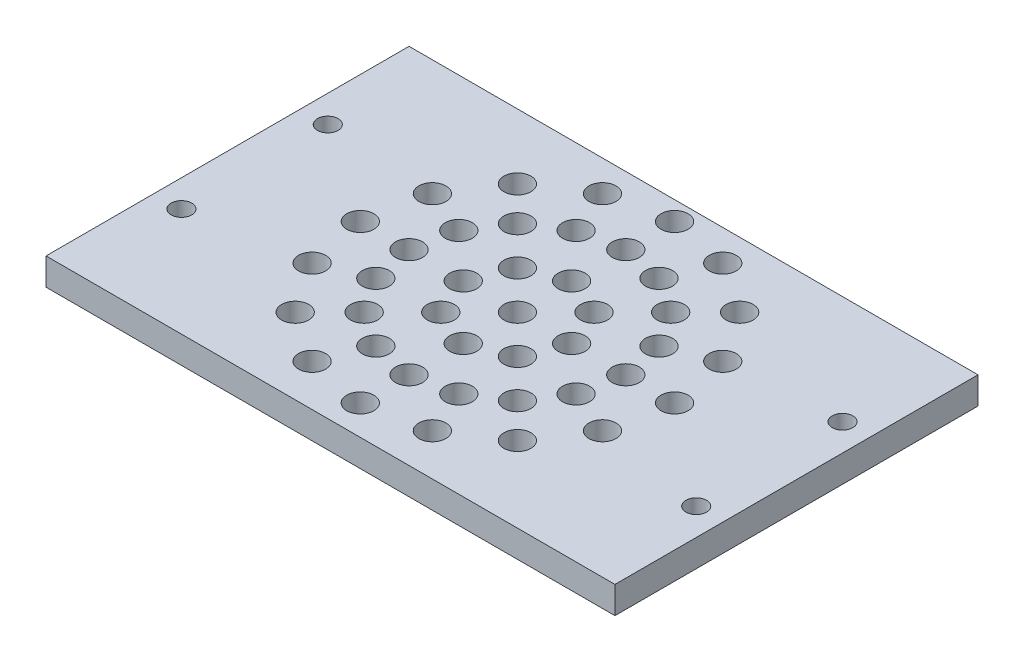
SolidWorks part; units mm, degrees
material "1060 Alloy"
ref_plane "Front Plane" through (0, 0, 0) normal (0, 0, 1) x (1, 0, 0)
ref_plane "Top Plane" through (0, 0, 0) normal (0, 1, 0) x (1, 0, 0)
ref_plane "Right Plane" through (0, 0, 0) normal (1, 0, 0) x (0, 0, -1)
sketch "Sketch1" plane through (0, 0, 0) normal (0, 1, 0) x (1, 0, 0)
  line L1 (-45.1884, 47.6545) -> (88.1616, 47.6545)
  line L2 (-45.1884, 47.6545) -> (-45.1884, -37.4355)
  line L3 (-45.1884, -37.4355) -> (88.1616, -37.4355)
  line L4 (88.1616, 47.6545) -> (88.1616, -37.4355)
  dimension "D1" = 133.35
  dimension "D2" = 85.09
extrude "Boss-Extrude1" add sketch "Sketch1" along normal blind 6.35
sketch "Sketch2" plane through (0, 6.35, 0) normal (0, 1, 0) x (1, 0, 0)
  line L0 (88.1616, -37.4355) -> (88.1616, 47.6545) construction
  line L1 (-45.1884, -37.4355) -> (88.1616, -37.4355) construction
  line L3 (88.1616, 47.6545) -> (-45.1884, 47.6545) construction
  line L4 (-45.1884, 47.6545) -> (-45.1884, -37.4355) construction
  circle A0 centre (81.8116, -12.0355) radius 2.413
  circle A1 centre (81.8116, 22.2545) radius 2.413
  circle A2 centre (-38.8384, 22.2545) radius 2.413
  circle A3 centre (-38.8384, -12.0355) radius 2.413
  point P0 (81.8116, -12.0355)
  point P1 (-38.8384, -12.0355)
  point P2 (81.8116, 22.2545)
  point P9 (-38.8384, 22.2545)
  dimension "D5" = 4.826
  dimension "D1" = 6.35
  dimension "D2" = 6.35
  dimension "D3" = 25.4
  dimension "D4" = 25.4
extrude "Cut-Extrude1" cut sketch "Sketch2" against normal through all
sketch "Sketch3" plane through (0, 6.35, 0) normal (0, 1, 0) x (1, 0, 0)
  line L0 (88.1616, -37.4355) -> (88.1616, 47.6545) construction
  line L2 (88.1616, 47.6545) -> (-45.1884, 47.6545) construction
  circle A0 centre (21.4866, 6.3795) radius 3.175
  circle A1 centre (34.1866, 6.3795) radius 3.175
  circle A2 centre (46.8866, 6.3795) radius 3.175
  circle A3 centre (30.4669, -2.6007) radius 3.175
  circle A4 centre (21.4866, -6.3205) radius 3.175
  circle A5 centre (12.5064, -2.6007) radius 3.175
  circle A6 centre (8.7866, 6.3795) radius 3.175
  circle A7 centre (12.5064, 15.3598) radius 3.175
  circle A8 centre (21.4866, 19.0795) radius 3.175
  circle A9 centre (30.4669, 15.3598) radius 3.175
  circle A10 centre (44.9532, -3.3406) radius 3.175
  circle A11 centre (39.4471, -11.581) radius 3.175
  circle A12 centre (31.2068, -17.087) radius 3.175
  circle A13 centre (21.4866, -19.0205) radius 3.175
  circle A14 centre (11.7665, -17.087) radius 3.175
  circle A15 centre (3.5261, -11.581) radius 3.175
  circle A16 centre (-1.9799, -3.3406) radius 3.175
  circle A17 centre (-3.9134, 6.3795) radius 3.175
  circle A18 centre (-1.9799, 16.0997) radius 3.175
  circle A19 centre (3.5261, 24.34) radius 3.175
  circle A20 centre (11.7665, 29.8461) radius 3.175
  circle A21 centre (21.4866, 31.7795) radius 3.175
  circle A22 centre (31.2068, 29.8461) radius 3.175
  circle A23 centre (39.4471, 24.34) radius 3.175
  circle A24 centre (44.9532, 16.0997) radius 3.175
  circle A25 centre (58.3166, 6.3795) radius 3.175
  circle A26 centre (55.5131, -7.7147) radius 3.175
  circle A27 centre (47.5294, -19.6632) radius 3.175
  circle A28 centre (35.5809, -27.6469) radius 3.175
  circle A29 centre (21.4866, -30.4505) radius 3.175
  circle A30 centre (7.3924, -27.6469) radius 3.175
  circle A31 centre (-4.5561, -19.6632) radius 3.175
  circle A32 centre (-12.5399, -7.7147) radius 3.175
  circle A33 centre (-15.3434, 6.3795) radius 3.175
  circle A34 centre (-12.5399, 20.4738) radius 3.175
  circle A35 centre (-4.5561, 32.4223) radius 3.175
  circle A36 centre (7.3924, 40.406) radius 3.175
  circle A37 centre (21.4866, 43.2095) radius 3.175
  circle A38 centre (35.5809, 40.406) radius 3.175
  circle A39 centre (47.5294, 32.4223) radius 3.175
  circle A40 centre (55.5131, 20.4738) radius 3.175
  point P26 (21.4866, 6.3795)
  point P57 (21.4866, 6.3795)
  point P91 (21.4866, 6.3795)
  dimension "D1" = 6.35
  dimension "D5" = 6.35
  dimension "D9" = 6.35
  dimension "D2" = 66.675
  dimension "D3" = 41.275
  dimension "D4" = 12.7
  dimension "D10" = 11.43
  dimension "D6" = 2
  dimension "D7" = 8
  dimension "D8" = 16
  dimension "D11" = 16
extrude "Cut-Extrude7" cut sketch "Sketch3" against normal through all
